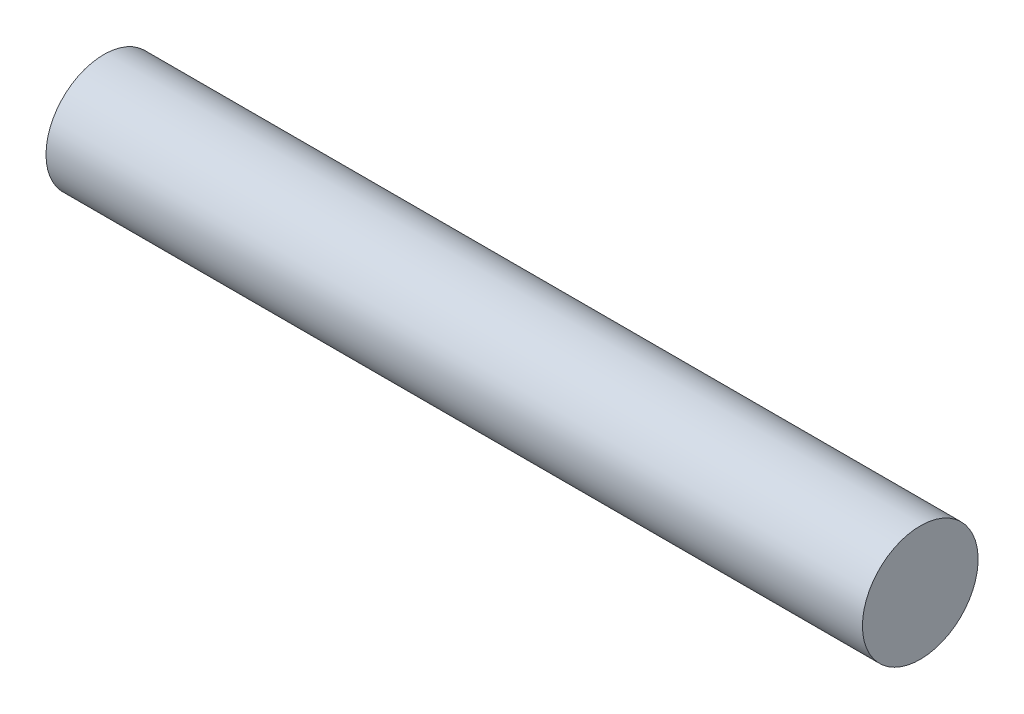
SolidWorks part; units mm, degrees
ref_plane "Front Plane" through (0, 0, 0) normal (0, 0, 1) x (1, 0, 0)
ref_plane "Top Plane" through (0, 0, 0) normal (0, 1, 0) x (1, 0, 0)
ref_plane "Right Plane" through (0, 0, 0) normal (1, 0, 0) x (0, 0, -1)
sketch "Sketch2" plane through (0, 0, 0) normal (0, 1, 0) x (1, 0, 0)
  line L0 (0, 0) -> (900, 0)
  line L1 (900, 0) -> (900, 63.75)
  line L2 (900, 63.75) -> (0, 63.75)
  line L3 (0, 63.75) -> (0, 0)
revolve "Revolve1" add sketch "Sketch2" angle 360 about L2 reverse direction yes
